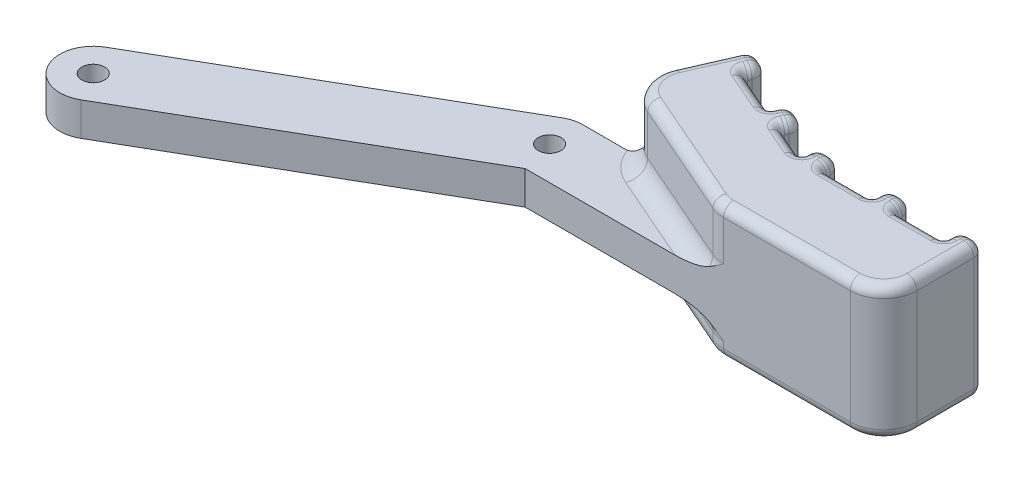
SolidWorks part; units mm, degrees
ref_plane "Front Plane" through (0, 0, 0) normal (0, 0, 1) x (1, 0, 0)
ref_plane "Top Plane" through (0, 0, 0) normal (0, 1, 0) x (1, 0, 0)
ref_plane "Right Plane" through (0, 0, 0) normal (1, 0, 0) x (0, 0, -1)
sketch "Sketch1" plane through (0, 0, 0) normal (0, 1, 0) x (1, 0, 0)
  line L0 (0, 0) -> (50, 0) construction
  line L1 (0, 5) -> (50, 5)
  line L2 (0, -5) -> (50, -5)
  arc A0 (0, 5) -> (0, -5) centre (0, 0) ccw
  arc A1 (50, -5) -> (50, 5) centre (50, 0) ccw
  circle A2 centre (0, 0) radius 1.7
  point P3 (25, 0)
  dimension "D1" = 5
  dimension "D3" = 3.4
  dimension "D2" = 50
extrude "Boss-Extrude1" add sketch "Sketch1" along normal blind 5
sketch "Sketch2" plane through (0, 0, 0) normal (0, -1, 0) x (1, 0, 0)
  line L0 (0, 0) -> (-43.3013, 25) construction
  line L1 (-2.5, -4.3301) -> (-45.8013, 20.6699)
  line L2 (2.5, 4.3301) -> (-40.8013, 29.3301)
  line L3 (0, 0) -> (49.8496, 0) construction
  arc A0 (-2.5, -4.3301) -> (2.5, 4.3301) centre (0, 0) ccw
  arc A1 (-40.8013, 29.3301) -> (-45.8013, 20.6699) centre (-43.3013, 25) ccw
  circle A2 centre (0, 0) radius 1.7
  circle A3 centre (-43.3013, 25) radius 1.7
  point P3 (-21.6506, 12.5)
  dimension "D1" = 5
  dimension "D2" = 3.4
  dimension "D4" = 3.4
  dimension "D3" = 150
  dimension "D5" = 50
extrude "Boss-Extrude2" add sketch "Sketch2" against normal blind 5
sketch "Sketch4" plane through (0, 0, 0) normal (0, -1, 0) x (1, 0, 0)
  line L0 (1.3397, 5) -> (50, 5) construction
  line L1 (31.0436, 5) -> (50, 5)
  line L2 (30, 5) -> (30, -8.5) construction
  line L3 (31.5, -10) -> (32, -10)
  line L4 (55, 0) -> (55, -8.5)
  line L5 (42.25, -10) -> (42.75, -10)
  line L7 (33.5, -8.5) -> (33.5, -8)
  line L8 (34, -7.5) -> (40.25, -7.5)
  line L9 (40.75, -8.5) -> (40.75, -8)
  line L11 (44.25, -8.5) -> (44.25, -8)
  line L12 (44.75, -7.5) -> (51, -7.5)
  line L13 (51.5, -8.5) -> (51.5, -8)
  line L14 (53, -10) -> (53.5, -10)
  line L15 (29.0436, 4.5826) -> (11.6697, -3)
  line L16 (9.0871, -9.5826) -> (12.0697, -16.4165)
  line L17 (30, -8.5) -> (30, -10) construction
  line L18 (30, -10) -> (55, -10) construction
  line L19 (55, -10) -> (55, -8.5) construction
  line L20 (14.0445, -17.1913) -> (14.5027, -16.9913)
  line L21 (15.2775, -15.0165) -> (15.0775, -14.5583)
  line L22 (15.3358, -13.9) -> (21.064, -11.4)
  line L23 (21.7222, -11.6583) -> (21.9222, -12.1165)
  line L24 (25.13, -10.7165) -> (24.93, -10.2583)
  line L25 (25.1883, -9.6) -> (29.3, -7.8055)
  line L26 (34, -7.5) -> (30, -7.5) construction
  line L27 (23.897, -12.8913) -> (24.3553, -12.6913)
  line L28 (30, -8.5) -> (30, -8.2638)
  line L29 (50, -5) -> (0, -5) construction
  arc A0 (50, -5) -> (50, 5) centre (50, 0) ccw construction
  arc A1 (50, 5) -> (55, 0) centre (50, 0) cw
  arc A2 (53.5, -10) -> (55, -8.5) centre (53.5, -8.5) ccw
  arc A3 (53, -10) -> (51.5, -8.5) centre (53, -8.5) cw
  arc A4 (42.75, -10) -> (44.25, -8.5) centre (42.75, -8.5) ccw
  arc A5 (42.25, -10) -> (40.75, -8.5) centre (42.25, -8.5) cw
  arc A6 (32, -10) -> (33.5, -8.5) centre (32, -8.5) ccw
  arc A7 (30, -8.5) -> (31.5, -10) centre (31.5, -8.5) ccw
  arc A8 (51, -7.5) -> (51.5, -8) centre (51, -8) cw
  arc A9 (44.25, -8) -> (44.75, -7.5) centre (44.75, -8) cw
  arc A10 (40.25, -7.5) -> (40.75, -8) centre (40.25, -8) cw
  arc A11 (33.5, -8) -> (34, -7.5) centre (34, -8) cw
  arc A12 (29.3, -7.8055) -> (30, -8.2638) centre (29.5, -8.2638) cw
  arc A13 (24.93, -10.2583) -> (25.1883, -9.6) centre (25.3883, -10.0583) cw
  arc A14 (21.064, -11.4) -> (21.7222, -11.6583) centre (21.264, -11.8583) cw
  arc A15 (15.0775, -14.5583) -> (15.3358, -13.9) centre (15.5358, -14.3583) cw
  arc A16 (25.13, -10.7165) -> (24.3553, -12.6913) centre (23.7553, -11.3165) cw
  arc A17 (21.9222, -12.1165) -> (23.897, -12.8913) centre (23.297, -11.5165) ccw
  arc A18 (15.2775, -15.0165) -> (14.5027, -16.9913) centre (13.9027, -15.6165) cw
  arc A19 (12.0697, -16.4165) -> (14.0445, -17.1913) centre (13.4445, -15.8165) ccw
  arc A20 (31.0436, 5) -> (29.0436, 4.5826) centre (31.0436, 0) ccw
  arc A21 (11.6697, -3) -> (9.0871, -9.5826) centre (13.6697, -7.5826) ccw
  point P16 (44.25, -8.25)
  point P22 (55, 5)
  point P24 (55, -10)
  point P27 (51.5, -10)
  point P30 (44.25, -10)
  point P35 (33.5, -10)
  point P40 (51.5, -7.5)
  point P43 (44.25, -7.5)
  point P46 (40.75, -7.5)
  point P49 (33.5, -7.5)
  point P67 (24.73, -9.8)
  point P70 (21.5222, -11.2)
  point P73 (14.8775, -14.1)
  point P76 (25.73, -12.0913)
  point P79 (22.5222, -13.4913)
  point P82 (15.8775, -16.3913)
  point P85 (12.6697, -17.7913)
  point P91 (7.0871, -5)
  dimension "D9" = 5
  dimension "D10" = 1.5
  dimension "D11" = 0.5
  dimension "D19" = 0.5
  dimension "D20" = 1.5
  dimension "D21" = 5
  dimension "D1" = 25
  dimension "D2" = 15
  dimension "D3" = 3.5
  dimension "D4" = 7.25
  dimension "D5" = 7.25
  dimension "D6" = 3.5
  dimension "D7" = 2.5
  dimension "D8" = 2.5
  dimension "D12" = 25
  dimension "D13" = 2.5
  dimension "D14" = 2.5
  dimension "D15" = 2.5
  dimension "D16" = 3.5
  dimension "D17" = 3.5
  dimension "D18" = 7.25
extrude "Boss-Extrude3" add sketch "Sketch4" along normal blind 5 and the other way blind 15
fillet "Fillet1" radius 2.5 7 edges at (9.3883, 2.5, -5) (10.3736, 5, -3.8228) (30.022, 5, 4.8945) (10.3736, 0, -3.8228) (30.022, 0, 4.8945) (20.3566, 5, 0.7913) (20.3566, 0, 0.7913)
fillet "Fillet2" radius 1.5 84 edges at (24.9228, 15, -9.8756) (25.03, 15, -10.4874) (25.1516, 15, -11.8644) (24.1261, 15, -12.7913) (22.7492, 15, -12.9129) (21.8222, 15, -11.8874) (21.4466, 15, -11.3928) (18.1999, 15, -12.65) (15.0703, 15, -14.1756) (15.1775, 15, -14.7874) (15.2991, 15, -16.1644) (14.2736, 15, -17.0913) (12.8966, 15, -17.2129) (10.5784, 15, -12.9995) (9.0151, 15, -5.7564) (20.3566, 15, 0.7913) (30.022, 15, 4.8945) (40.5218, 15, 5) (53.5355, 15, 3.5355) (55, 15, -4.25) (54.5607, 15, -9.5607) (53.25, 15, -10) (51.9393, 15, -9.5607) (51.5, 15, -8.25) (51.3536, 15, -7.6464) (47.875, 15, -7.5) (44.3964, 15, -7.6464) (44.25, 15, -8.25) (43.8107, 15, -9.5607) (42.5, 15, -10) (41.1893, 15, -9.5607) (40.75, 15, -8.25) (40.6036, 15, -7.6464) (37.125, 15, -7.5) (33.6464, 15, -7.6464) (33.5, 15, -8.25) (33.0607, 15, -9.5607) (31.75, 15, -10) (30.4393, 15, -9.5607) (30, 15, -8.3819) (29.7739, 15, -7.8454) (53.5355, -5, 3.5355) (55, -5, -4.25) (54.5607, -5, -9.5607) (53.25, -5, -10) (51.9393, -5, -9.5607) (51.5, -5, -8.25) (51.3536, -5, -7.6464) (47.875, -5, -7.5) (44.3964, -5, -7.6464) (44.25, -5, -8.25) (43.8107, -5, -9.5607) (42.5, -5, -10) (41.1893, -5, -9.5607) (40.75, -5, -8.25) (40.6036, -5, -7.6464) (37.125, -5, -7.5) (33.6464, -5, -7.6464) (33.5, -5, -8.25) (33.0607, -5, -9.5607) (31.75, -5, -10) (30.4393, -5, -9.5607) (30, -5, -8.3819) (29.7739, -5, -7.8454) (27.2441, -5, -8.7028) (24.9228, -5, -9.8756) (25.03, -5, -10.4874) (25.1516, -5, -11.8644) (24.1261, -5, -12.7913) (22.7492, -5, -12.9129) (21.8222, -5, -11.8874) (21.4466, -5, -11.3928) (18.1999, -5, -12.65) (15.0703, -5, -14.1756) (15.1775, -5, -14.7874) (15.2991, -5, -16.1644) (14.2736, -5, -17.0913) (12.8966, -5, -17.2129) (10.5784, -5, -12.9995) (9.0151, -5, -5.7564) (20.3566, -5, 0.7913) (30.022, -5, 4.8945) (27.2441, 15, -8.7028) (40.5218, -5, 5)
